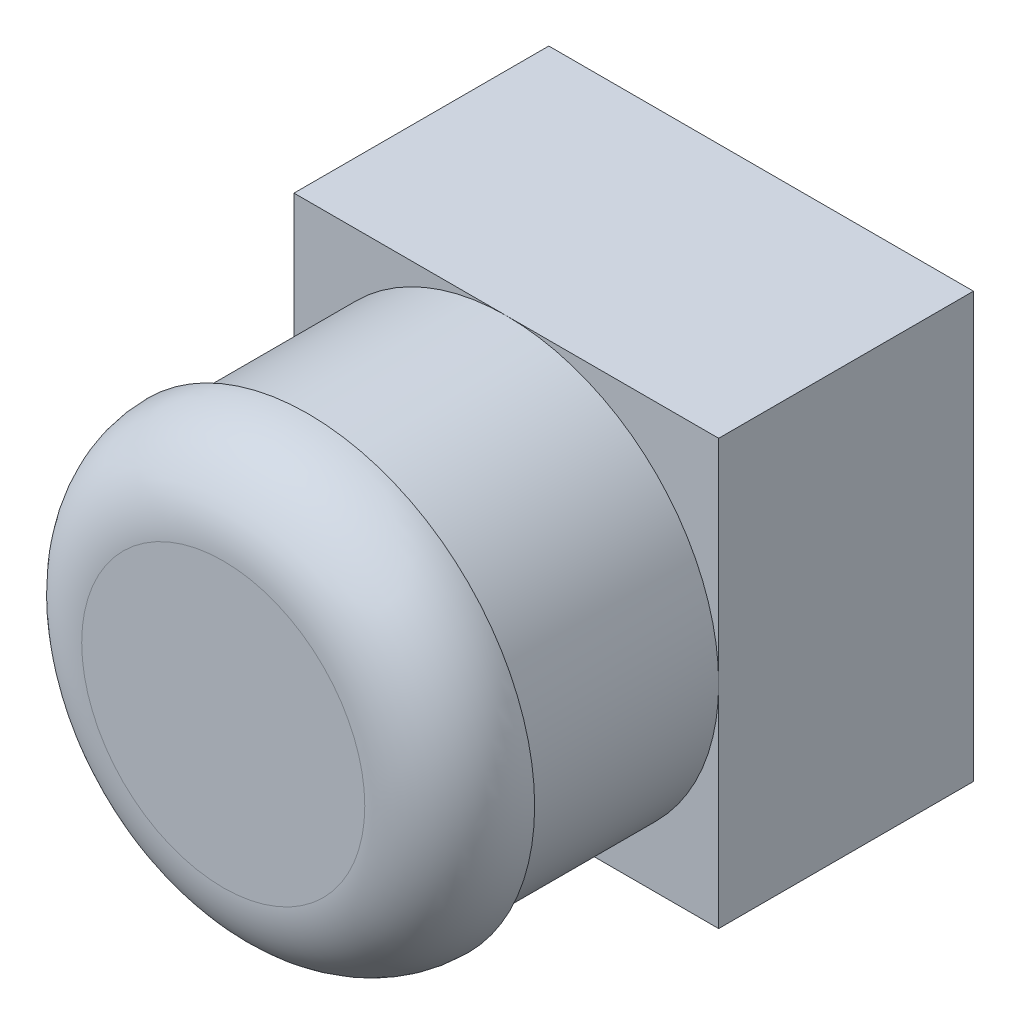
SolidWorks part; units mm, degrees
ref_plane "前视基准面" through (0, 0, 0) normal (0, 0, 1) x (1, 0, 0)
ref_plane "上视基准面" through (0, 0, 0) normal (0, 1, 0) x (1, 0, 0)
ref_plane "右视基准面" through (0, 0, 0) normal (1, 0, 0) x (0, 0, -1)
sketch "草图1" plane through (0, 0, 0) normal (0, 0, 1) x (1, 0, 0)
  line L0 (-7.5, -7.5) -> (7.5, -7.5)
  line L1 (-7.5, -7.5) -> (-7.5, 7.5)
  line L2 (7.5, -7.5) -> (7.5, 7.5)
  line L3 (-7.5, 7.5) -> (7.5, 7.5)
  line L4 (-7.5, -7.5) -> (7.5, 7.5) construction
  line L5 (7.5, -7.5) -> (-7.5, 7.5) construction
  point P1 (0, 0)
  dimension "D1" = 15
  dimension "D2" = 15
extrude "凸台-拉伸1" add sketch "草图1" along normal blind 9
sketch "草图5" plane through (0, 0, 9) normal (0, 0, 1) x (1, 0, 0)
  circle A0 centre (0, 0) radius 7.5
extrude "凸台-拉伸2" add sketch "草图5" along normal blind 7
sketch "草图6" plane through (0, 0, 16) normal (0, 0, 1) x (1, 0, 0)
  circle A0 centre (0, 0) radius 8
extrude "凸台-拉伸3" add sketch "草图6" along normal blind 3
fillet "圆角1" radius 3 1 edges at (8, 0, 19)
